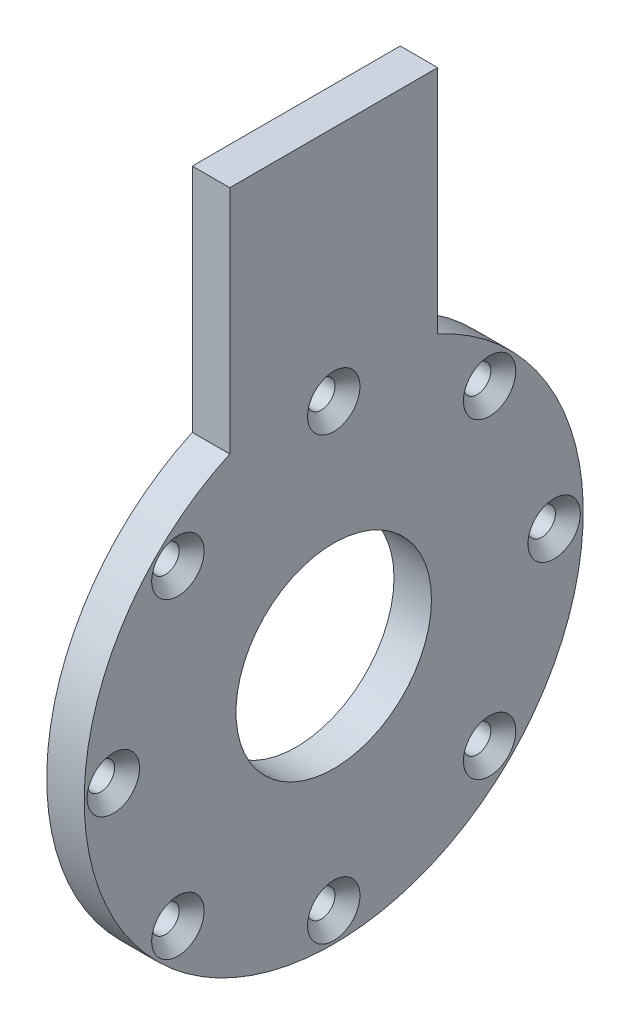
SolidWorks part; units mm, degrees
material "6061 Alloy"
ref_plane "Front Plane" through (0, 0, 0) normal (0, 0, 1) x (1, 0, 0)
ref_plane "Top Plane" through (0, 0, 0) normal (0, 1, 0) x (1, 0, 0)
ref_plane "Right Plane" through (0, 0, 0) normal (1, 0, 0) x (0, 0, -1)
sketch "Sketch1" plane through (0, 0, 0) normal (1, 0, 0) x (0, 0, -1)
  line L0 (-25, 110) -> (25, 110)
  line L1 (0, 0) -> (0, 110) construction
  line L2 (-25, 110) -> (-25, 54.5436)
  line L3 (25, 110) -> (25, 54.5436)
  arc A0 (-25, 54.5436) -> (25, 54.5436) centre (0, 0) ccw
  circle A1 centre (0, 0) radius 23.5
  point P7 (0, 110)
  dimension "D1" = 120
  dimension "D2" = 47
  dimension "D3" = 50
  dimension "D4" = 50
extrude "Boss-Extrude1" add sketch "Sketch1" along normal blind 9 and the other way blind 0.01
sketch "Sketch2" plane through (9, 0, 0) normal (1, 0, 0) x (0, 0, -1)
  circle A0 centre (0, 0) radius 53
  arc A1 (-25, 54.5436) -> (25, 54.5436) centre (0, 0) ccw construction
  point P6 (0, 53)
  point P9 (37.4767, 37.4767)
  point P10 (53, 0)
  point P11 (37.4767, -37.4767)
  point P12 (0, -53)
  point P13 (-37.4767, -37.4767)
  point P14 (-53, 0)
  point P15 (-37.4767, 37.4767)
  dimension "D1" = 7
  dimension "D2" = 8
hole_wizard "CSK for M6 Countersunk Flat Head Screw1" positions "Sketch2" profile "Sketch3" countersink size "M6" standard "ISO" end condition through all
sketch "Sketch3" plane through (9, 37.4767, 37.4767) normal (0, 1, 0) x (0, 0, -1)
  line L0 (0, 0) -> (0, 9.01)
  line L1 (0, 9.01) -> (3.3, 9.01)
  line L2 (3.3, 9.01) -> (3.3, 3)
  line L3 (3.3, 3) -> (6.3, 0)
  line L5 (6.3, 0) -> (0, 0)
  line L6 (-3.3, 3) -> (-6.3, 0) construction
  line L11 (0, -6.35) -> (0, 107.95) construction
  dimension "Thru Hole Dia." = 6.6
  dimension "Thru Hole Depth" = 9.01
  dimension "Near C'Sink Dia." = 12.6
  dimension "Near C'Sink Angle" = 90
